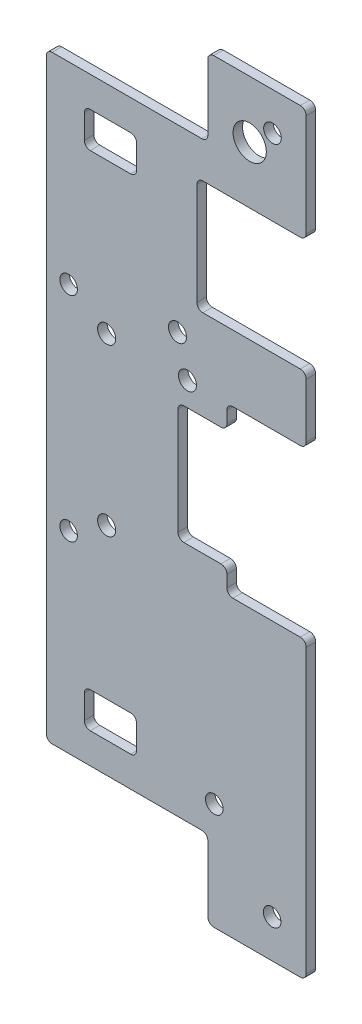
SolidWorks part; units mm, degrees
material "Thornel Mat VMA"
ref_plane "Front Plane" through (0, 0, 0) normal (0, 0, 1) x (1, 0, 0)
ref_plane "Top Plane" through (0, 0, 0) normal (0, 1, 0) x (1, 0, 0)
ref_plane "Right Plane" through (0, 0, 0) normal (1, 0, 0) x (0, 0, -1)
sketch "Sketch1" plane through (0, 0, 0) normal (0, 0, 1) x (1, 0, 0)
  line L0 (-2.9301, -104.5098) -> (-3.3149, -104.5098)
  line L1 (-3.3149, -72.8868) -> (-2.9301, -72.8868)
  line L78 (45.3299, -66.5368) -> (45.3299, -72.8868)
  line L79 (45.3299, -104.5098) -> (45.3299, -110.8598)
  line L80 (66.5174, -66.5368) -> (105.3971, 12.1397)
  line L81 (105.3971, 12.1397) -> (38.7094, 12.1397)
  line L88 (38.7094, 12.1397) -> (38.7094, -8.6883)
  line L89 (-2.9301, -8.6883) -> (38.7094, -8.6883)
  line L90 (-3.3149, -53.8368) -> (-2.9301, -53.8368)
  line L91 (-2.9301, -53.8368) -> (-2.9301, -8.6883)
  line L92 (-3.3149, -66.5368) -> (-3.3149, -53.8368)
  line L93 (-3.3149, -72.8868) -> (-3.3149, -66.5368)
  line L94 (-2.9301, -104.5098) -> (-2.9301, -72.8868)
  line L95 (-3.3149, -110.8598) -> (-3.3149, -104.5098)
  line L96 (66.5174, -110.8598) -> (105.3971, -189.5363)
  line L97 (105.3971, -189.5363) -> (38.7094, -189.5363)
  line L98 (38.7094, -189.5363) -> (38.7094, -168.7083)
  line L99 (-2.9301, -168.7083) -> (38.7094, -168.7083)
  line L106 (-3.3149, -110.8598) -> (-3.3149, -123.5598)
  line L107 (-3.3149, -123.5598) -> (-2.9301, -123.5598)
  line L108 (66.5174, -110.8598) -> (45.3299, -110.8598)
  line L109 (45.3299, -66.5368) -> (66.5174, -66.5368)
  line L110 (45.3299, -104.5098) -> (45.3299, -72.8868)
  line L111 (-2.9301, -123.5598) -> (-2.9301, -168.7083)
  circle A0 centre (90.6739, 2.6147) radius 2.3495
  circle A1 centre (41.9566, -16.4353) radius 2.3495
  circle A2 centre (3.0351, -60.1868) radius 2.3495
  circle A3 centre (3.0351, -117.2098) radius 2.3495
  circle A4 centre (41.9566, -160.9613) radius 2.3495
  circle A5 centre (90.6739, -180.0113) radius 2.3495
  circle A6 centre (51.4094, -3.1003) radius 4.445
  point P2 (90.6739, 2.6147)
  point P4 (41.9566, -16.4353)
  point P6 (3.0351, -60.1868)
  point P8 (3.0351, -117.2098)
  point P10 (41.9566, -160.9613)
  point P11 (90.6739, -180.0113)
  dimension "D2" = 4.699
  dimension "D5" = 8.89
  dimension "D1" = 66.6876
  dimension "D3" = 12.7
  dimension "D4" = 15.24
  dimension "D6" = 48.26
extrude "Boss-Extrude1" add sketch "Sketch1" along normal blind 2.54
sketch "Sketch2" plane through (0, 0, 2.54) normal (0, 0, 1) x (1, 0, 0)
  line L0 (-3.3149, -53.8368) -> (-3.3149, -72.8868) construction
  line L1 (45.3299, -66.5368) -> (66.5174, -66.5368) construction
  line L2 (45.3299, -88.6983) -> (-2.9301, -88.6983) construction
  line L3 (45.3299, -110.8598) -> (45.3299, -66.5368) construction
  line L4 (-2.9301, -72.8868) -> (-2.9301, -104.5098) construction
  circle A0 centre (13.1951, -66.5368) radius 2.413
  circle A2 centre (34.7851, -66.5368) radius 2.413
  circle A4 centre (34.7851, -110.8598) radius 2.413
  circle A6 centre (13.1951, -110.8598) radius 2.413
  dimension "D1" = 4.826
  dimension "D2" = 21.59
  dimension "D3" = 4.826
  dimension "D5" = 16.51
  dimension "D7" = 0
extrude "Cut-Extrude1" cut sketch "Sketch2" against normal through all
sketch "Sketch3" plane through (0, 0, 2.54) normal (0, 0, 1) x (1, 0, 0)
  line L0 (45.3299, -110.8598) -> (45.3299, -66.5368) construction
  line L1 (45.3299, -72.8868) -> (32.2451, -72.8868)
  line L2 (45.3299, -72.8868) -> (45.3299, -104.5098)
  line L3 (45.3299, -104.5098) -> (32.2451, -104.5098)
  line L4 (32.2451, -72.8868) -> (32.2451, -104.5098)
  line L5 (45.3299, -66.5368) -> (66.5174, -66.5368) construction
  line L6 (66.5174, -110.8598) -> (45.3299, -110.8598) construction
  circle A1 centre (13.1951, -66.5368) radius 2.413 construction
  dimension "D3" = 19.05
  dimension "D1" = 6.35
  dimension "D2" = 6.35
extrude "Cut-Extrude2" cut sketch "Sketch3" against normal through all
sketch "Sketch4" plane through (0, 0, 2.54) normal (0, 0, 1) x (1, 0, 0)
  line L0 (-2.9301, -168.7083) -> (38.7094, -168.7083) construction
  line L1 (27.4577, 15.7469) -> (40.2334, 15.7469)
  line L2 (27.4577, 15.7469) -> (27.4577, -8.6883)
  line L3 (27.4577, -8.6883) -> (40.2334, -8.6883)
  line L4 (40.2334, 15.7469) -> (40.2334, -8.6883)
  line L5 (0, -197.042) -> (40.2334, -197.042)
  line L6 (0, -197.042) -> (0, -168.7083)
  line L7 (0, -168.7083) -> (40.2334, -168.7083)
  line L8 (40.2334, -197.042) -> (40.2334, -168.7083)
  line L9 (38.7094, -168.7083) -> (38.7094, -189.5363) construction
  line L10 (38.7094, -8.6883) -> (-2.9301, -8.6883) construction
  dimension "D1" = 1.524
extrude "Cut-Extrude3" cut sketch "Sketch4" against normal through all
sketch "Sketch5" plane through (0, 0, 0) normal (0, 0, -1) x (-1, 0, 0)
  line L0 (2.9301, -8.6883) -> (2.9301, -53.8368) construction
  line L1 (-40.2334, -8.6883) -> (2.9301, -8.6883) construction
  circle A0 centre (-32.1219, -22.4043) radius 2.413
  circle A1 centre (-32.1219, -56.6943) radius 2.413
  dimension "D4" = 4.826
  dimension "D1" = 35.052
  dimension "D2" = 13.716
  dimension "D3" = 34.29
extrude "Cut-Extrude4" cut sketch "Sketch5" against normal through all
sketch "Sketch7" plane through (0, 0, 2.54) normal (0, 0, 1) x (1, 0, 0)
  line L0 (66.5174, -66.5368) -> (66.5174, 21.5221)
  line L1 (66.5174, 21.5221) -> (127.8208, 21.5221)
  line L2 (66.5174, -110.8598) -> (66.5174, -200.2563)
  line L3 (66.5174, -200.2563) -> (115.7822, -200.2563)
  line L4 (115.7822, -200.2563) -> (127.8208, 21.5221)
  line L5 (66.5174, -66.5368) -> (66.5174, -110.8598)
extrude "Cut-Extrude5" cut sketch "Sketch7" against normal through all both and the other way through all
extrude "Cut-Extrude6" cut sketch "Sketch8" against normal through all
sketch "Sketch8" plane through (-2.1864, -156.0179, 0) normal (0, 0, -1) x (0.9999, -0.0134, 0)
  circle A0 centre (57.5716, -158.8222) radius 2.3495
  circle A1 centre (59.8998, 22.5177) radius 2.3495
fillet "Fillet1" radius 1.5875 16 edges at (-2.9301, -168.7083, 1.27) (40.2334, -168.7083, 1.27) (40.2334, -189.5363, 1.27) (66.5174, -189.5363, 1.27) (66.5174, -110.8598, 1.27) (45.3299, -110.8598, 1.27) (45.3299, -104.5098, 1.27) (32.2451, -104.5098, 1.27) (32.2451, -72.8868, 1.27) (45.3299, -72.8868, 1.27) (45.3299, -66.5368, 1.27) (66.5174, -66.5368, 1.27) (66.5174, 12.1397, 1.27) (40.2334, 12.1397, 1.27) (40.2334, -8.6883, 1.27) (-2.9301, -8.6883, 1.27)
sketch "Sketch9" plane through (0, -123.5598, 0) normal (0, -1, 0) x (1, 0, 0)
  line L1 (-3.3149, 2.54) -> (-2.9301, 2.54)
  line L2 (-3.3149, 2.54) -> (-3.3149, 0)
  line L3 (-3.3149, 0) -> (-2.9301, 0)
  line L4 (-2.9301, 2.54) -> (-2.9301, 0)
extrude "Cut-Extrude7" cut sketch "Sketch9" against normal through all
sketch "Sketch10" plane through (0, 0, 0) normal (0, 0, -1) x (-1, 0, 0)
  line L0 (-40.2334, -7.1008) -> (-40.2334, 10.5522) construction
  line L1 (-37.3074, -18.3403) -> (-66.5174, -18.3403)
  line L2 (-37.3074, -18.3403) -> (-37.3074, -48.8203)
  line L3 (-37.3074, -48.8203) -> (-66.5174, -48.8203)
  line L4 (-66.5174, -18.3403) -> (-66.5174, -48.8203)
  line L5 (-66.5174, 10.5522) -> (-66.5174, -64.9493) construction
  line L6 (-38.6459, -8.6883) -> (1.3426, -8.6883) construction
  line L7 (2.9301, -10.2758) -> (2.9301, -167.1208) construction
  line L8 (-7.2299, -16.8163) -> (-21.1999, -16.8163)
  line L9 (-7.2299, -16.8163) -> (-7.2299, -26.3413)
  line L10 (-7.2299, -26.3413) -> (-21.1999, -26.3413)
  line L11 (-21.1999, -16.8163) -> (-21.1999, -26.3413)
  line L12 (-32.2451, -88.6983) -> (2.9301, -88.6983) construction
  line L13 (-32.2451, -74.4743) -> (-32.2451, -102.9223) construction
  line L14 (-21.1999, -160.5803) -> (-21.1999, -151.0553)
  line L15 (-7.2299, -151.0553) -> (-21.1999, -151.0553)
  line L16 (-7.2299, -160.5803) -> (-7.2299, -151.0553)
  line L17 (-7.2299, -160.5803) -> (-21.1999, -160.5803)
  line L18 (-64.9299, 12.1397) -> (-41.8209, 12.1397) construction
  dimension "D1" = 30.48
  dimension "D2" = 29.21
  dimension "D3" = 8.128
  dimension "D4" = 9.525
  dimension "D5" = 10.16
  dimension "D6" = 13.97
  dimension "D7" = 30.48
extrude "Cut-Extrude8" cut sketch "Sketch10" against normal blind 2.54
sketch "Sketch12" plane through (0, 0, 0) normal (0, 0, -1) x (-1, 0, 0)
  line L0 (-46.5451, -18.3403) -> (-37.3074, -18.3403)
  line L1 (-43.3317, -18.3403) -> (-66.5174, -18.3403) construction
  line L2 (-37.3074, -18.3403) -> (-37.3074, -26.6795)
  line L3 (-37.3074, -48.8203) -> (-37.3074, -18.3403) construction
  line L4 (-37.3074, -26.6795) -> (-21.1999, -26.6795)
  line L5 (-21.1999, -16.8163) -> (-21.1999, -26.3413) construction
  line L6 (-21.1999, -26.6795) -> (-21.1999, -16.8163)
  line L7 (-21.1999, -16.8163) -> (-46.5451, -12.5328)
  line L8 (-46.5451, -12.5328) -> (-46.5451, -18.3403)
  line L9 (-33.8326, -104.5098) -> (-43.7424, -104.5098) construction
  line L10 (-40.1395, -107.4088) -> (-27.7341, -107.4088)
  line L11 (-40.1395, -107.4088) -> (-40.1395, -114.3781)
  line L12 (-40.1395, -114.3781) -> (-27.7341, -114.3781)
  line L13 (-27.7341, -107.4088) -> (-27.7341, -114.3781)
  line L14 (-45.3299, -109.2723) -> (-45.3299, -106.0973) construction
  dimension "D1" = 5.8075
  dimension "D2" = 8.3393
  dimension "D3" = 25.3451
  dimension "D4" = 12.4054
  dimension "D5" = 6.9693
  dimension "D6" = 2.899
  dimension "D7" = 5.1904
extrude "Boss-Extrude2" add sketch "Sketch12" against normal up to surface (2.54 mm away) up to face at (14.2149, -21.5788, 2.54)
fillet "Fillet2" radius 1.5875 12 edges at (21.1999, -160.5803, 1.27) (21.1999, -151.0553, 1.27) (7.2299, -151.0553, 1.27) (7.2299, -160.5803, 1.27) (21.1999, -26.3413, 1.27) (21.1999, -16.8163, 1.27) (7.2299, -16.8163, 1.27) (7.2299, -26.3413, 1.27) (66.5174, -48.8203, 1.27) (37.3074, -48.8203, 1.27) (37.3074, -18.3403, 1.27) (66.5174, -18.3403, 1.27)
